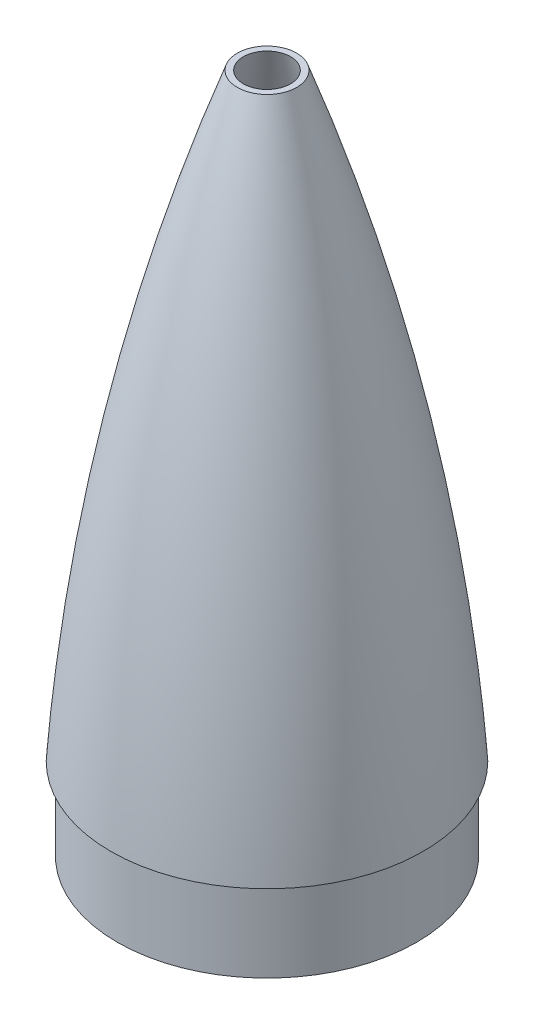
SolidWorks part; units mm, degrees
material "PVB"
ref_plane "Front Plane" through (0, 0, 0) normal (0, 0, 1) x (1, 0, 0)
ref_plane "Top Plane" through (0, 0, 0) normal (0, 1, 0) x (1, 0, 0)
ref_plane "Right Plane" through (0, 0, 0) normal (1, 0, 0) x (0, 0, -1)
sketch "Sketch2" plane through (0, 0, 0) normal (0, 0, 1) x (1, 0, 0)
  line L0 (0, 0) -> (0, 330.2) construction
  line L1 (-76.2, 0) -> (-69.85, 0)
  line L2 (0, 330.2) -> (0, 325.12)
  arc A0 (0, 330.2) -> (-76.2, 0) centre (1014.3906, -77.7824) ccw
  arc A1 (0, 325.12) -> (-69.85, 0) centre (1133.5772, -88.4854) ccw
  dimension "D1" = 330.2
  dimension "D2" = 5.08
  dimension "D3" = 76.2
  dimension "D4" = 6.35
revolve "Revolve1" add sketch "Sketch2" angle 360 about L2
ref_plane "Plane2" through (0, 381, 0) normal (0, 1, 0) x (1, 0, 0)
sketch "Sketch7" plane through (0, 381, 0) normal (0, 1, 0) x (1, 0, 0)
  circle A0 centre (0, 0) radius 317.5
  dimension "D1" = 635
extrude "Cut-Extrude2" cut sketch "Sketch7" against normal blind 88.9
sketch "Sketch8" plane through (0, 0, 0) normal (0, -1, 0) x (1, 0, 0)
  circle A0 centre (0, 0) radius 69.85
  circle A1 centre (0, 0) radius 73.025
  dimension "D1" = 146.05
extrude "Boss-Extrude1" add sketch "Sketch8" along normal blind 40
